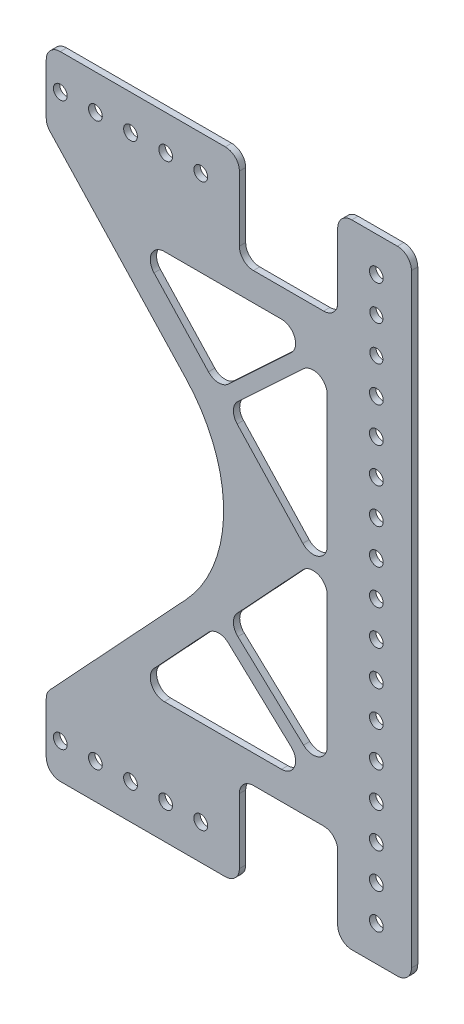
SolidWorks part; units mm, degrees
ref_plane "Front Plane" through (0, 0, 0) normal (0, 0, 1) x (1, 0, 0)
ref_plane "Top Plane" through (0, 0, 0) normal (0, 1, 0) x (1, 0, 0)
ref_plane "Right Plane" through (0, 0, 0) normal (1, 0, 0) x (0, 0, -1)
sketch "Sketch1" plane through (0, 0, 0) normal (0, 0, 1) x (1, 0, 0)
  line L11 (65.4076, 898.4977) -> (48.8976, 898.4977)
  line L12 (43.8176, 893.4177) -> (43.8176, 869.9227)
  line L13 (38.7376, 864.8427) -> (13.3376, 864.8427)
  line L14 (8.2576, 869.9227) -> (8.2576, 893.4177)
  line L15 (3.1776, 898.4977) -> (-56.5124, 898.4977)
  line L16 (-60.2304, 871.6349) -> (-11.0513, 818.8143)
  line L17 (70.4876, 893.4177) -> (70.4876, 784.1977)
  line L18 (-61.5924, 875.0965) -> (-61.5924, 893.4177)
  line L20 (-22.6122, 846.1411) -> (-2.9253, 824.9965)
  line L21 (40.0076, 791.7957) -> (40.0076, 839.4169)
  line L22 (23.5028, 854.6827) -> (-18.8942, 854.6827)
  line L23 (70.4876, 674.9777) -> (70.4876, 784.1977)
  line L24 (65.4076, 669.8977) -> (48.8976, 669.8977)
  line L25 (43.8176, 674.9777) -> (43.8176, 698.4727)
  line L26 (38.7376, 703.5527) -> (13.3376, 703.5527)
  line L27 (8.2576, 698.4727) -> (8.2576, 674.9777)
  line L28 (-60.2304, 696.7606) -> (-11.0513, 749.5812)
  line L29 (3.1776, 669.8977) -> (-56.5124, 669.8977)
  line L30 (-61.5924, 693.2989) -> (-61.5924, 674.9777)
  line L31 (26.9645, 845.8848) -> (4.2543, 824.7402)
  line L32 (7.4596, 754.5529) -> (31.2096, 780.0614)
  line L33 (31.4659, 843.1349) -> (7.716, 821.0222)
  line L34 (7.4596, 813.8426) -> (31.2096, 788.3341)
  line L35 (40.0076, 776.5997) -> (40.0076, 728.9785)
  line L36 (31.4659, 725.2606) -> (7.716, 747.3732)
  line L37 (26.9645, 722.5107) -> (4.2543, 743.6552)
  line L38 (-22.6122, 722.2544) -> (-2.9253, 743.3989)
  line L39 (23.5028, 713.7127) -> (-18.8942, 713.7127)
  arc A1 (65.4076, 898.4977) -> (70.4876, 893.4177) centre (65.4076, 893.4177) cw
  arc A2 (48.8976, 898.4977) -> (43.8176, 893.4177) centre (48.8976, 893.4177) ccw
  arc A3 (43.8176, 869.9227) -> (38.7376, 864.8427) centre (38.7376, 869.9227) cw
  arc A4 (13.3376, 864.8427) -> (8.2576, 869.9227) centre (13.3376, 869.9227) cw
  arc A5 (8.2576, 893.4177) -> (3.1776, 898.4977) centre (3.1776, 893.4177) ccw
  arc A6 (-56.5124, 898.4977) -> (-61.5924, 893.4177) centre (-56.5124, 893.4177) ccw
  circle A7 centre (-31.1124, 885.7977) radius 2.4892
  circle A8 centre (-18.4124, 885.7977) radius 2.4892
  circle A9 centre (-5.7124, 885.7977) radius 2.4892
  circle A11 centre (57.7876, 860.3977) radius 2.3719
  circle A12 centre (57.7876, 847.6977) radius 2.4892
  circle A13 centre (57.7876, 834.9977) radius 2.4892
  circle A14 centre (57.7876, 822.2977) radius 2.4892
  circle A15 centre (57.7876, 809.5977) radius 2.4892
  arc A16 (-60.2304, 871.6349) -> (-61.5924, 875.0965) centre (-56.5124, 875.0965) cw
  arc A17 (31.2096, 788.3341) -> (40.0076, 791.7957) centre (34.9276, 791.7957) ccw
  arc A18 (-22.6122, 846.1411) -> (-18.8942, 854.6827) centre (-18.8942, 849.6027) cw
  arc A19 (65.4076, 669.8977) -> (70.4876, 674.9777) centre (65.4076, 674.9777) ccw
  arc A20 (48.8976, 669.8977) -> (43.8176, 674.9777) centre (48.8976, 674.9777) cw
  arc A21 (43.8176, 698.4727) -> (38.7376, 703.5527) centre (38.7376, 698.4727) ccw
  arc A22 (13.3376, 703.5527) -> (8.2576, 698.4727) centre (13.3376, 698.4727) ccw
  arc A23 (8.2576, 674.9777) -> (3.1776, 669.8977) centre (3.1776, 674.9777) cw
  circle A24 centre (-5.7124, 682.5977) radius 2.4892
  circle A25 centre (-18.4124, 682.5977) radius 2.4892
  circle A26 centre (-31.1124, 682.5977) radius 2.4892
  arc A27 (-60.2304, 696.7606) -> (-61.5924, 693.2989) centre (-56.5124, 693.2989) ccw
  arc A28 (-56.5124, 669.8977) -> (-61.5924, 674.9777) centre (-56.5124, 674.9777) cw
  circle A29 centre (57.7876, 733.3977) radius 2.4892
  circle A30 centre (57.7876, 720.6977) radius 2.4892
  circle A31 centre (57.7876, 707.9977) radius 2.4892
  circle A32 centre (57.7876, 682.5977) radius 2.4892
  circle A33 centre (57.7876, 885.7977) radius 2.4892
  arc A34 (-11.0513, 818.8143) -> (-11.0513, 749.5812) centre (-48.231, 784.1977) cw
  circle A35 centre (57.7876, 771.4977) radius 2.4892
  circle A36 centre (57.7876, 758.7977) radius 2.4892
  circle A37 centre (57.7876, 746.0977) radius 2.4892
  circle A38 centre (-56.5124, 885.7977) radius 2.4892
  circle A39 centre (-43.8124, 885.7977) radius 2.4892
  circle A40 centre (-43.8124, 682.5977) radius 2.4892
  circle A41 centre (-56.5124, 682.5977) radius 2.4892
  arc A42 (7.716, 821.0222) -> (7.4596, 813.8426) centre (11.1776, 817.3043) ccw
  arc A43 (31.4659, 843.1349) -> (40.0076, 839.4169) centre (34.9276, 839.4169) cw
  arc A44 (26.9645, 845.8848) -> (23.5028, 854.6827) centre (23.5028, 849.6027) ccw
  arc A45 (4.2543, 824.7402) -> (-2.9253, 824.9965) centre (0.7927, 828.4582) cw
  arc A46 (31.2096, 780.0614) -> (40.0076, 776.5997) centre (34.9276, 776.5997) cw
  arc A47 (7.716, 747.3732) -> (7.4596, 754.5529) centre (11.1776, 751.0912) cw
  arc A48 (31.4659, 725.2606) -> (40.0076, 728.9785) centre (34.9276, 728.9785) ccw
  arc A49 (26.9645, 722.5107) -> (23.5028, 713.7127) centre (23.5028, 718.7927) cw
  arc A50 (4.2543, 743.6552) -> (-2.9253, 743.3989) centre (0.7927, 739.9373) ccw
  arc A51 (-22.6122, 722.2544) -> (-18.8942, 713.7127) centre (-18.8942, 718.7927) ccw
  circle A52 centre (57.7876, 796.8977) radius 2.4892
  circle A53 centre (57.7876, 784.1977) radius 2.4892
  circle A54 centre (57.7876, 873.0977) radius 2.3719
  circle A55 centre (57.7876, 695.2977) radius 2.4892
  point P14 (70.4876, 784.1977)
  point P17 (45.0876, 784.1977)
  dimension "D1" = 10.16
  dimension "D3" = 5.08
  dimension "D4" = 50.8
  dimension "D5" = 5.08
  dimension "D6" = 5.08
  dimension "D8" = 5.08
  dimension "D11" = 12.7
  dimension "D12" = 12.7
  dimension "D2" = 10.16
  dimension "D7" = 5.08
  dimension "D9" = 3
  dimension "D10" = 2
extrude "Boss-Extrude2" add sketch "Sketch1" along normal blind 2.286 contours L16 A34 L28 A27 L30 A28 L29 A23 L27 A22 L26 A21 L25 A20 L24 A19 L23 L17 A1 L11 A2 L12 A3 L13 A4 L14 A5 L15 A6 L18 A16 A55 A54 A53 A52 A51 L38 A50 L37 A49 L39 A48 L36 A47 L32 region at (15.2139, 784.2164, 0)
sketch "Sketch2" [suppressed] plane through (0, 0, 0) normal (0, 0, -1) x (-1, 0, 0)
  line L0 (-70.4876, 784.1977) -> (29.7113, 784.1977) construction
  line L1 (-70.4876, 674.9777) -> (-70.4876, 893.4177) construction
  circle A0 centre (-26.4815, 826.617) radius 2.54
  circle A1 centre (-30.3527, 804.0119) radius 2.54
  circle A2 centre (-12.2581, 845.8816) radius 2.54
  circle A3 centre (5.9262, 840.3002) radius 2.54
  circle A4 centre (5.9262, 728.0952) radius 2.54
  circle A5 centre (-12.2581, 722.5139) radius 2.54
  circle A6 centre (-30.3527, 764.3835) radius 2.54
  circle A7 centre (-26.4815, 741.7785) radius 2.54
  dimension "D1" = 5.08
